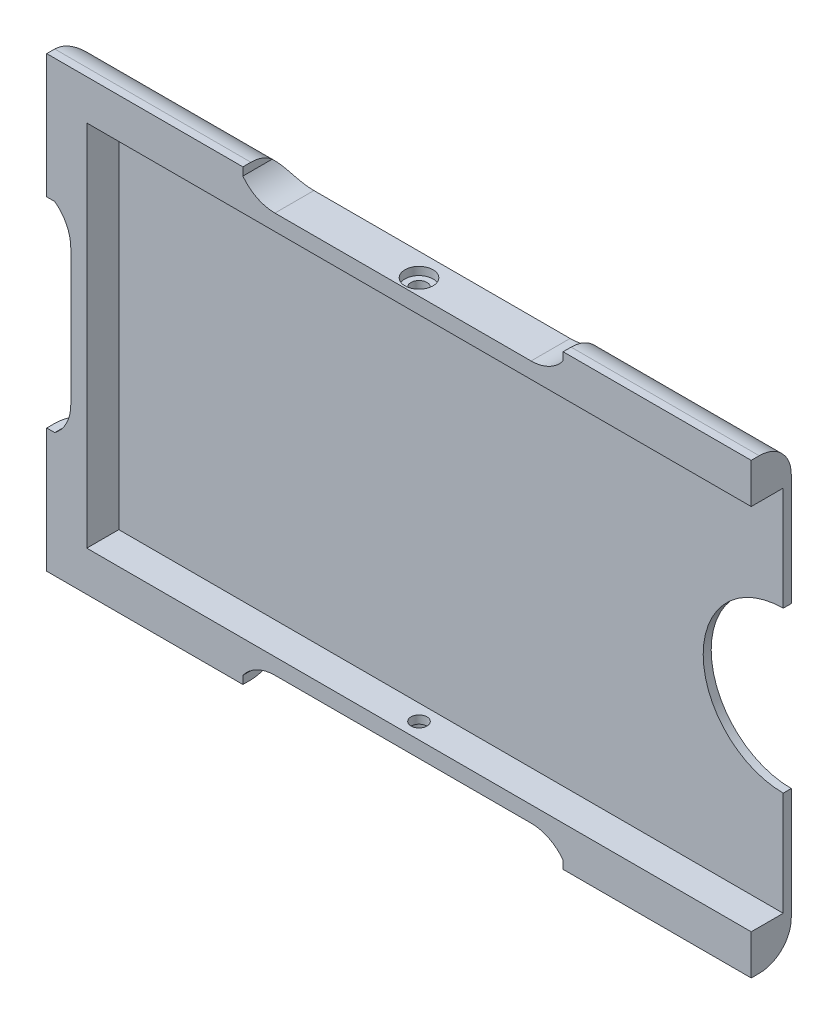
SolidWorks part; units mm, degrees
ref_plane "Front" through (0, 0, 0) normal (0, 0, 1) x (1, 0, 0)
ref_plane "Top" through (0, 0, 0) normal (0, 1, 0) x (1, 0, 0)
ref_plane "Right" through (0, 0, 0) normal (1, 0, 0) x (0, 0, -1)
sketch "Çizim4" plane through (0, 0, 0) normal (0, 0, 1) x (1, 0, 0)
  line L0 (202.8156, -67.0774) -> (202.8156, -82.0774)
  line L1 (202.8156, -67.0774) -> (202.8156, -64.0774)
  line L2 (202.8156, -64.0774) -> (179.3156, -64.0774)
  line L3 (114.8156, -64.0774) -> (114.8156, -79.5774)
  line L4 (114.8156, -120.0774) -> (139.3156, -120.0774)
  line L5 (202.8156, -120.0774) -> (202.8156, -117.0774)
  line L6 (179.3156, -119.0774) -> (179.3156, -120.0774)
  line L7 (179.3156, -120.0774) -> (202.8156, -120.0774)
  line L8 (139.3156, -119.0774) -> (139.3156, -120.0774)
  line L9 (139.3156, -65.0774) -> (139.3156, -64.0774)
  line L10 (202.8156, -102.0774) -> (202.8156, -117.0774)
  line L11 (115.8156, -79.5774) -> (114.8156, -79.5774)
  line L12 (115.8156, -104.5774) -> (114.8156, -104.5774)
  line L13 (114.8156, -104.5774) -> (114.8156, -120.0774)
  line L14 (175.3156, -117.0774) -> (143.3156, -117.0774)
  line L15 (117.8156, -83.5774) -> (117.8156, -100.5774)
  line L16 (175.3156, -67.0774) -> (143.3156, -67.0774)
  line L17 (179.3156, -65.0774) -> (179.3156, -64.0774)
  line L18 (139.3156, -64.0774) -> (114.8156, -64.0774)
  arc A0 (179.3156, -119.0774) -> (175.3156, -117.0774) centre (175.3156, -122.0774) ccw
  arc A1 (143.3156, -117.0774) -> (139.3156, -119.0774) centre (143.3156, -122.0774) ccw
  arc A2 (115.8156, -104.5774) -> (117.8156, -100.5774) centre (112.8156, -100.5774) ccw
  arc A3 (117.8156, -83.5774) -> (115.8156, -79.5774) centre (112.8156, -83.5774) ccw
  arc A4 (139.3156, -65.0774) -> (143.3156, -67.0774) centre (143.3156, -62.0774) ccw
  arc A5 (175.3156, -67.0774) -> (179.3156, -65.0774) centre (175.3156, -62.0774) ccw
  arc A6 (202.8156, -82.0774) -> (202.8156, -102.0774) centre (202.8156, -92.0774) ccw
  point P31 (127.0656, -120.0774)
  point P34 (159.3156, -117.0774)
  point P35 (0, 0)
  dimension "D1" = 10
  dimension "D2" = 88
  dimension "D3" = 56
  dimension "D4" = 3
  dimension "D5" = 3
  dimension "D6" = 3
  dimension "D7" = 28
extrude "Yükseklik-Ekstrüzyon1" add sketch "Çizim4" along normal blind 5
sketch "Çizim6" plane through (0, 0, 5) normal (0, 0, 1) x (1, 0, 0)
  line L0 (202.8156, -82.0774) -> (202.8156, -64.0774) construction
  line L1 (119.8156, -69.0774) -> (202.8156, -69.0774)
  line L2 (119.8156, -69.0774) -> (119.8156, -115.0774)
  line L3 (119.8156, -115.0774) -> (202.8156, -115.0774)
  line L4 (202.8156, -69.0774) -> (202.8156, -115.0774)
  line L5 (139.3156, -64.0774) -> (114.8156, -64.0774) construction
  line L6 (114.8156, -104.5774) -> (114.8156, -120.0774) construction
  line L7 (114.8156, -120.0774) -> (139.3156, -120.0774) construction
  dimension "D1" = 5
  dimension "D2" = 5
  dimension "D3" = 5
extrude "Kes-Ekstrüzyon2" cut sketch "Çizim6" against normal blind 4
fillet "Radyus1" radius 4 3 edges at (114.8156, -112.3274, 0) (127.0656, -120.0774, 0) (191.0656, -64.0774, 0)
sketch "Çizim7" plane through (0, -67.0774, 0) normal (0, 1, 0) x (1, 0, 0)
  line L0 (118.8156, 0) -> (202.8156, 0) construction
  circle A0 centre (159.3156, -3) radius 1
  dimension "D1" = 2
  dimension "D2" = 3
extrude "Kes-Ekstrüzyon3" cut sketch "Çizim7" against normal blind 1000
sketch "Çizim9" plane through (0, -117.0774, 0) normal (0, -1, 0) x (-1, 0, 0)
  circle A0 centre (-159.3156, -3) radius 1.75
  dimension "D1" = 3.5
extrude "Kes-Ekstrüzyon5" cut sketch "Çizim9" against normal blind 1
sketch "Çizim10" plane through (0, -67.0774, 0) normal (0, 1, 0) x (1, 0, 0)
  circle A0 centre (159.3156, -3) radius 1.75
  dimension "D1" = 3.5
extrude "Kes-Ekstrüzyon6" cut sketch "Çizim10" against normal blind 1
